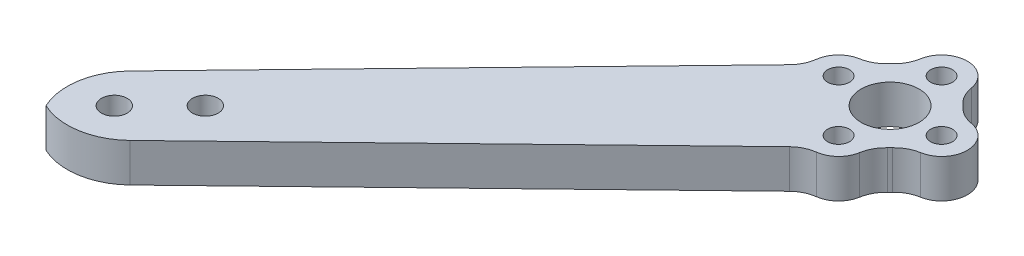
SolidWorks part; units mm, degrees
ref_plane "Front Plane" through (0, 0, 0) normal (0, 0, 1) x (1, 0, 0)
ref_plane "Top Plane" through (0, 0, 0) normal (0, 1, 0) x (1, 0, 0)
ref_plane "Right Plane" through (0, 0, 0) normal (1, 0, 0) x (0, 0, -1)
sketch "Sketch1" plane through (0, 0, 0) normal (0, 1, 0) x (1, 0, 0)
  line L1 (85, -85) -> (-85, -85) construction
  line L2 (85, -85) -> (85, 85) construction
  line L3 (85, 85) -> (-85, 85) construction
  line L4 (-85, -85) -> (-85, 85) construction
  line L5 (85, -85) -> (-85, 85) construction
  line L6 (85, 85) -> (-85, -85) construction
  point P0 (0, 0)
  dimension "D1" = 170
  dimension "D2" = 170
sketch "Sketch7" plane through (0, 0, 0) normal (0, 1, 0) x (1, 0, 0)
  line L0 (85, -85) -> (-85, 85) construction
  line L1 (25, -25) -> (-25, -25) construction
  line L2 (25, -25) -> (25, 25) construction
  line L3 (25, 25) -> (-25, 25) construction
  line L4 (-25, -25) -> (-25, 25) construction
  line L5 (25, -25) -> (-25, 25) construction
  line L6 (25, 25) -> (-25, -25) construction
  circle A0 centre (24.7487, 24.7487) radius 2
  circle A1 centre (31.8198, 31.8198) radius 2
  point P0 (0, 0)
  dimension "D2" = 4
  dimension "D3" = 4
  dimension "D1" = 50
  dimension "D4" = 35
  dimension "D5" = 45
sketch "Sketch2" plane through (0, 0, 0) normal (0, 1, 0) x (1, 0, 0)
  line L7 (82.7012, 71.6708) -> (23.5806, 14.468)
  line L10 (14.468, 23.5806) -> (71.6708, 82.7012)
  line L23 (14.468, 23.5806) -> (23.5806, 14.468)
  arc A0 (79.539, 90.8462) -> (79.1538, 90.461) centre (85, 85) ccw
  circle A4 centre (85, 93) radius 1.7
  circle A5 centre (93, 85) radius 1.7
  circle A6 centre (85, 77) radius 1.7
  circle A7 centre (77, 85) radius 1.7
  arc A8 (76.3333, 88.9441) -> (73.0344, 85.5236) centre (77, 85) ccw
  arc A9 (88.9441, 93.6667) -> (81.0559, 93.6667) centre (85, 93) ccw
  arc A10 (93.6667, 81.0559) -> (93.6667, 88.9441) centre (93, 85) ccw
  arc A11 (85.5236, 73.0344) -> (88.9441, 76.3333) centre (85, 77) ccw
  arc A12 (90.8462, 90.461) -> (90.461, 90.8462) centre (85, 85) ccw
  arc A13 (90.461, 79.1538) -> (90.8462, 79.539) centre (85, 85) ccw
  arc A15 (93.6667, 81.0559) -> (90.8462, 79.539) centre (94.5, 76.1259) ccw
  arc A16 (90.461, 79.1538) -> (88.9441, 76.3333) centre (93.8741, 75.5) ccw
  arc A17 (79.539, 90.8462) -> (81.0559, 93.6667) centre (76.1259, 94.5) ccw
  arc A18 (76.3333, 88.9441) -> (79.1538, 90.461) centre (75.5, 93.8741) ccw
  arc A19 (93.6667, 88.9441) -> (90.8462, 90.461) centre (94.5, 93.8741) cw
  arc A20 (88.9441, 93.6667) -> (90.461, 90.8462) centre (93.8741, 94.5) ccw
  arc A23 (85.5236, 73.0344) -> (82.7012, 71.6708) centre (86.178, 68.0774) ccw
  arc A24 (73.0344, 85.5236) -> (71.6708, 82.7012) centre (68.0774, 86.178) cw
  circle A82 centre (85, 85) radius 4.5
  point P28 (92, 88.873)
  point P146 (0, 0)
  dimension "D1" = 5
  dimension "D2" = 5
  dimension "D5" = 5
extrude "Boss-Extrude1" add sketch "Sketch2" along normal blind 6
sketch "Sketch6" plane through (0, 0, 0) normal (0, 1, 0) x (1, 0, 0)
  circle A0 centre (85, 85) radius 14 construction
  circle A1 centre (85, 85) radius 63.5 construction
  circle A2 centre (85, -85) radius 63.5 construction
  circle A3 centre (-85, -85) radius 63.5 construction
  circle A4 centre (-85, 85) radius 63.5 construction
fillet "Fillet1" radius 10 2 edges at (23.5806, 3, -14.468) (14.468, 3, -23.5806)
extrude "Cut-Extrude2" cut sketch "Sketch7" against normal through all both and the other way through all
